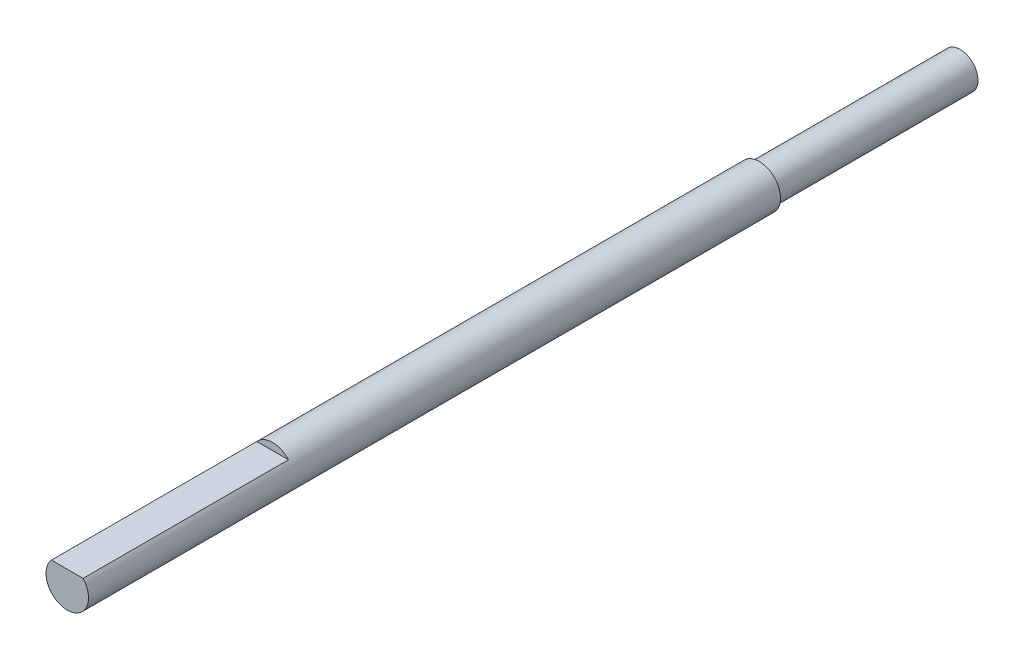
SolidWorks part; units mm, degrees
ref_plane "Front Plane" through (0, 0, 0) normal (0, 0, 1) x (1, 0, 0)
ref_plane "Top Plane" through (0, 0, 0) normal (0, 1, 0) x (1, 0, 0)
ref_plane "Right Plane" through (0, 0, 0) normal (1, 0, 0) x (0, 0, -1)
sketch "Sketch1" plane through (0, 0, 0) normal (0, 0, 1) x (1, 0, 0)
  circle A0 centre (0, 0) radius 4.7625
  dimension "D1" = 9.525
extrude "Boss-Extrude1" add sketch "Sketch1" along normal blind 200
sketch "Sketch2" plane through (0, 0, 200) normal (0, 0, 1) x (1, 0, 0)
  line L0 (0, 0) -> (0, 3.175) construction
  line L1 (-3.5498, 3.175) -> (3.5498, 3.175)
  circle A0 centre (0, 0) radius 4.7625
  circle M2 centre (0, 0) radius 4.7625
  dimension "D2" = 9.525
  dimension "D1" = 3.175
extrude "Cut-Extrude1" cut sketch "Sketch2" against normal blind 46 contours L1 M2 region at (0, 3.82, 200)
sketch "Sketch3" plane through (0, 0, 0) normal (0, 0, -1) x (-1, 0, 0)
  circle A0 centre (0, 0) radius 4.7625
  circle A1 centre (0, 0) radius 4
  dimension "D1" = 9.525
  dimension "D2" = 8
extrude "Cut-Extrude2" cut sketch "Sketch3" against normal blind 45
